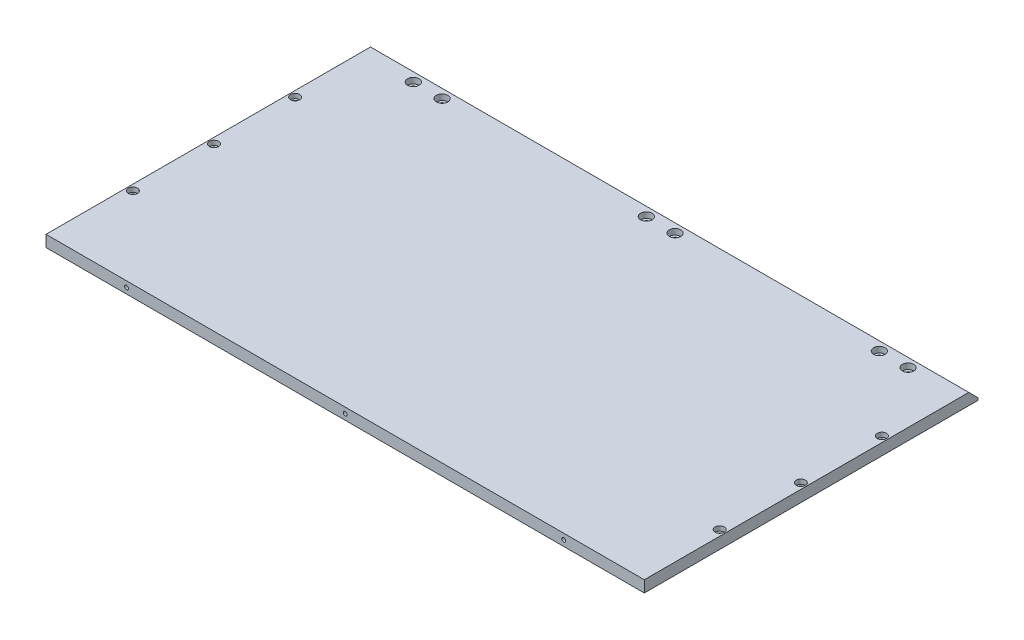
SolidWorks part; units mm, degrees
material "Bakelite Black"
ref_plane "Front" through (0, 0, 0) normal (0, 0, 1) x (1, 0, 0)
ref_plane "Top" through (0, 0, 0) normal (0, 1, 0) x (1, 0, 0)
ref_plane "Right" through (0, 0, 0) normal (1, 0, 0) x (0, 0, -1)
sketch "Sketch1" plane through (0, 0, 0) normal (0, 1, 0) x (1, 0, 0)
  line L1 (-260, 290) -> (260, 290)
  line L2 (-260, 290) -> (-260, 0)
  line L3 (-260, 0) -> (260, 0)
  line L4 (260, 290) -> (260, 0)
  line L5 (-260, 290) -> (260, 0) construction
  line L6 (-260, 0) -> (260, 290) construction
  point P0 (0, 145)
  dimension "D1" = 520
  dimension "D2" = 290
extrude "Boss-Extrude1" add sketch "Sketch1" along normal blind 10
hole_wizard "CBORE for M5 SHCS1" positions "Sketch3" profile "Sketch4" counterbore size "M5" standard "ANSI Metric"
sketch "Sketch3" plane through (0, 10, 0) normal (0, 1, 0) x (1, 0, 0)
  line L0 (0, -50) -> (0, 50) construction
  line L1 (260, 290) -> (-260, 290) construction
  point P0 (-215, 274.25)
  point P2 (-190, 274.25)
  point P4 (-12.5, 274.25)
  point P6 (12.5, 274.25)
  point P8 (190, 274.25)
  point P10 (215, 274.25)
  dimension "D1" = 12.5
  dimension "D2" = 12.5
  dimension "D3" = 25
  dimension "D4" = 25
  dimension "D5" = 190
  dimension "D6" = 190
  dimension "D7" = 15.75
sketch "Sketch4" plane through (-215, 10, -274.25) normal (1, 0, 0) x (0, 0, 1)
  line L0 (0, 0) -> (0, 13.1524)
  line L1 (0, 13.1524) -> (2.75, 11.5)
  line L2 (2.75, 11.5) -> (2.75, 5)
  line L3 (2.75, 5) -> (5, 5)
  line L4 (5, 5) -> (5, 0)
  line L5 (5, 0) -> (0, 0)
  line L10 (0, 13.1524) -> (-2.75, 11.5) construction
  line L11 (0, -6.35) -> (0, 107.95) construction
  dimension "Hole Dia." = 5.5
  dimension "Hole Depth" = 11.5
  dimension "C'Bore Dia." = 10
  dimension "C'Bore Depth" = 5
  dimension "Drill Angle" = 118
sketch "Sketch2" plane through (0, 0, 0) normal (1, 0, 0) x (0, 0, -1)
  line L0 (290, 2) -> (290, 10)
  line L1 (290, 10) -> (290, 0) construction
  line L2 (290, 10) -> (282, 10)
  line L3 (290, 10) -> (0, 10) construction
  line L4 (282, 10) -> (290, 2)
  dimension "D1" = 8
  dimension "D2" = 8
extrude "Cut-Extrude1" cut sketch "Sketch2" against normal through all both and the other way through all
hole_wizard "CBORE for M4 SHCS1" positions "Sketch5" profile "Sketch6" counterbore size "M4" standard "ANSI Metric" end condition through all
sketch "Sketch5" plane through (0, 10, 0) normal (0, 1, 0) x (1, 0, 0)
  line L0 (-260, 0) -> (260, 0) construction
  line L1 (260, 0) -> (260, 282) construction
  point P0 (255, 211.5)
  point P2 (255, 141)
  point P4 (255, 70.5)
  dimension "D1" = 70.5
  dimension "D2" = 70.5
  dimension "D3" = 70.5
  dimension "D4" = 5
sketch "Sketch6" plane through (255, 10, -211.5) normal (1, 0, 0) x (0, 0, 1)
  line L0 (0, 0) -> (0, 10)
  line L1 (0, 10) -> (2.25, 10)
  line L3 (2.25, 10) -> (2.25, 4)
  line L4 (2.25, 4) -> (4, 4)
  line L5 (4, 4) -> (4, 0)
  line L7 (4, 0) -> (0, 0)
  line L11 (0, -6.35) -> (0, 107.95) construction
  dimension "Thru Hole Dia." = 4.5
  dimension "Thru Hole Depth" = 10
  dimension "C'Bore Dia." = 8
  dimension "C'Bore Depth" = 4
mirror "Mirror1" about plane through (0, 0, 0) normal (1, 0, 0) of "CBORE for M4 SHCS1"
hole_wizard "M4x0.7 Tapped Hole1" positions "Sketch7" profile "Sketch8" tap size "M4x0.7" standard "ANSI Metric"
sketch "Sketch7" plane through (0, 0, 0) normal (0, 0, 1) x (1, 0, 0)
  line L0 (0, -50) -> (0, 50) construction
  line L1 (-260, 10) -> (260, 10) construction
  point P0 (-190, 5)
  point P2 (0, 5)
  point P4 (190, 5)
  dimension "D1" = 190
  dimension "D2" = 190
  dimension "D3" = 5
sketch "Sketch8" plane through (-190, 5, 0) normal (1, 0, 0) x (0, -1, 0)
  line L0 (0, 0) -> (0, 12.9914)
  line L1 (0, 12.9914) -> (1.65, 12)
  line L2 (1.65, 12) -> (1.65, 0)
  line L5 (1.65, 0) -> (0, 0)
  line L10 (0, 12.9914) -> (-1.65, 12) construction
  line L11 (0, -6.35) -> (0, 107.95) construction
  dimension "Tap Drill Dia." = 3.3
  dimension "Tap Drill Depth" = 12
  dimension "Drill Angle" = 118
cosmetic thread "Hole Thread1" parameters "D1"=8, "D2"=4
cosmetic thread "Hole Thread2" parameters "D1"=8, "D2"=4
cosmetic thread "Hole Thread3" parameters "D1"=8, "D2"=4
